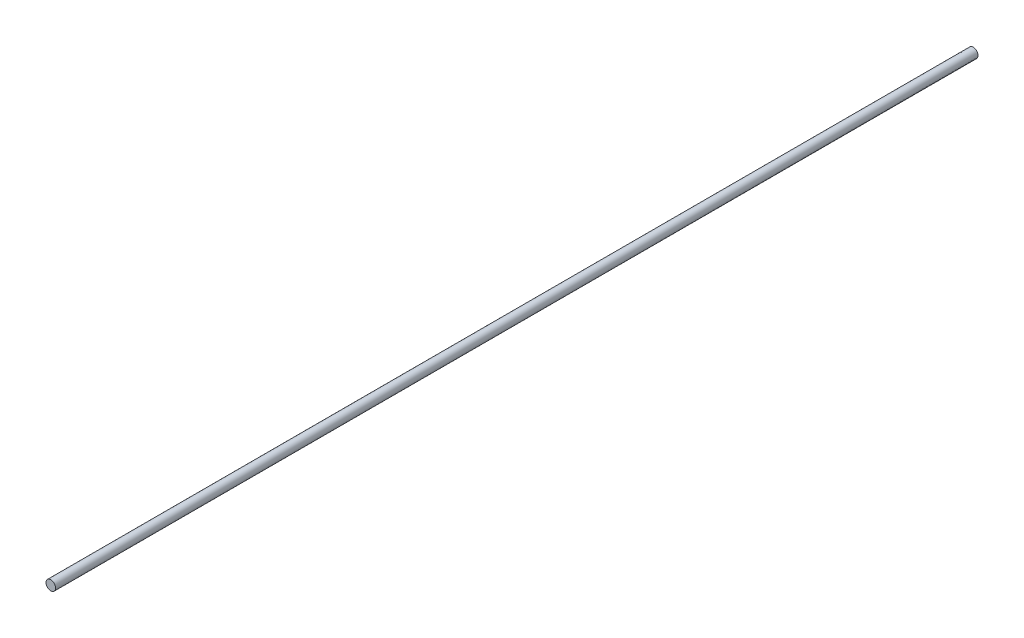
SolidWorks part; units mm, degrees
ref_plane "Front Plane" through (0, 0, 0) normal (0, 0, 1) x (1, 0, 0)
ref_plane "Top Plane" through (0, 0, 0) normal (0, 1, 0) x (1, 0, 0)
ref_plane "Right Plane" through (0, 0, 0) normal (1, 0, 0) x (0, 0, -1)
sketch "Sketch1" plane through (0, 0, 0) normal (0, 0, 1) x (1, 0, 0)
  circle A0 centre (0, 0) radius 0.7937
  dimension "D1" = 1.5875
extrude "Boss-Extrude1" add sketch "Sketch1" along normal blind 152.4
